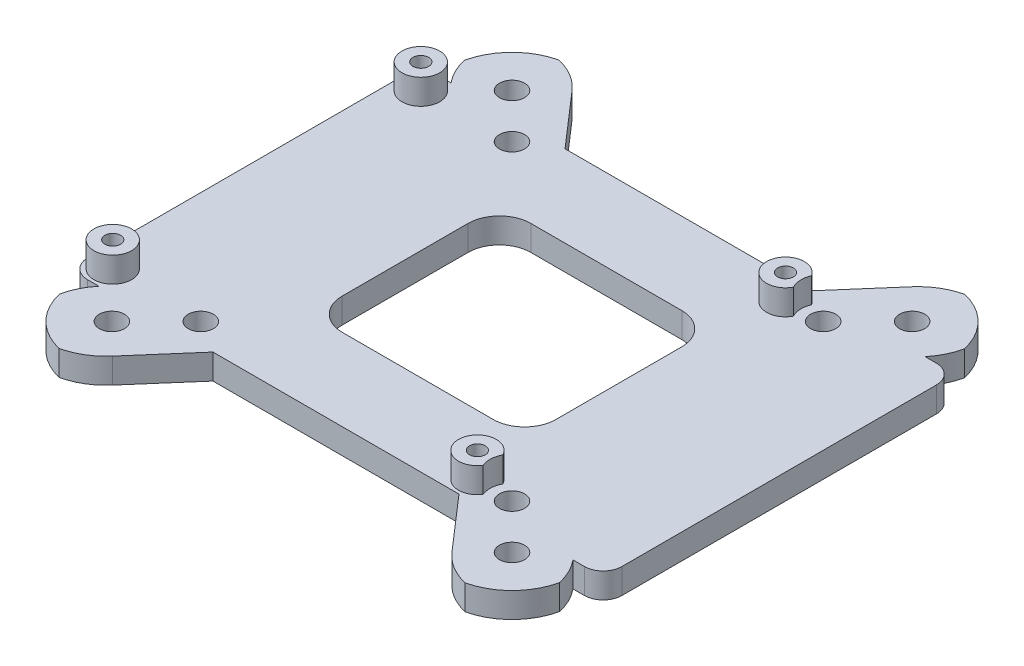
SolidWorks part; units mm, degrees
ref_plane "Front Plane" through (0, 0, 0) normal (0, 0, 1) x (1, 0, 0)
ref_plane "Top Plane" through (0, 0, 0) normal (0, 1, 0) x (1, 0, 0)
ref_plane "Right Plane" through (0, 0, 0) normal (1, 0, 0) x (0, 0, -1)
sketch "Sketch1" plane through (0, 0, 0) normal (0, 1, 0) x (1, 0, 0)
  line L1 (-42.5, -28) -> (42.5, -28)
  line L2 (-42.5, -28) -> (-42.5, 28)
  line L3 (-42.5, 28) -> (42.5, 28)
  line L4 (42.5, -28) -> (42.5, 28)
  line L5 (-12, -15) -> (12, -15)
  line L6 (-17, -10) -> (-17, 10)
  line L7 (-12, 15) -> (12, 15)
  line L8 (17, -10) -> (17, 10)
  line L9 (-17, -15) -> (17, 15) construction
  line L10 (-17, 15) -> (17, -15) construction
  circle A0 centre (-39, 24.5) radius 1.25
  circle A1 centre (-39, -24.5) radius 1.25
  circle A5 centre (19, 24.5) radius 1.25
  circle A6 centre (19, -24.5) radius 1.25
  arc A7 (-12, -15) -> (-17, -10) centre (-12, -10) cw
  arc A8 (12, -15) -> (17, -10) centre (12, -10) ccw
  arc A9 (17, 10) -> (12, 15) centre (12, 10) ccw
  arc A10 (-17, 10) -> (-12, 15) centre (-12, 10) cw
  point P0 (0, 0)
  point P14 (0, 0)
  dimension "D3" = 3.5
  dimension "D7" = 3.5
  dimension "D11" = 34
  dimension "D13" = 5
  dimension "D1" = 85
  dimension "D2" = 56
  dimension "D4" = 3.5
  dimension "D5" = 3.5
  dimension "D6" = 3.5
  dimension "D8" = 3.5
  dimension "D9" = 58
  dimension "D10" = 58
  dimension "D12" = 30
extrude "Boss-Extrude1" add sketch "Sketch1" along normal blind 4 contours L1 L4 L3 L2 region at (-41.4821, 0, 0)
sketch "Sketch2" plane through (0, 4, 0) normal (0, 1, 0) x (1, 0, 0)
  circle A0 centre (-39, 24.5) radius 3
  circle A1 centre (19, 24.5) radius 3
  circle A2 centre (19, -24.5) radius 3
  circle A3 centre (-39, -24.5) radius 3
  circle A4 centre (-39, 24.5) radius 1.25
  circle A5 centre (19, 24.5) radius 1.25
  circle A6 centre (19, -24.5) radius 1.25
  circle A7 centre (-39, -24.5) radius 1.25
extrude "Boss-Extrude2" add sketch "Sketch2" along normal blind 4
sketch "Sketch4" plane through (0, 4, 0) normal (0, 1, 0) x (1, 0, 0)
  line L1 (-40, -40) -> (40, -40)
  line L2 (-40, -40) -> (-40, 40)
  line L3 (-40, 40) -> (40, 40)
  line L4 (40, -40) -> (40, 40)
  line L5 (-40, -40) -> (40, 40) construction
  line L6 (-40, 40) -> (40, -40) construction
  point P0 (0, 0)
  dimension "D1" = 80
  dimension "D2" = 80
fillet "Fillet1" radius 3 4 edges at (42.5, 2, -28) (42.5, 2, 28) (-42.5, 2, 28) (-42.5, 2, -28)
sketch "Sketch5" plane through (0, 0, 0) normal (0, 1, 0) x (1, 0, 0)
  line L1 (15, -15) -> (-15, -15) construction
  line L2 (15, -15) -> (15, 15) construction
  line L3 (15, 15) -> (-15, 15) construction
  line L4 (-15, -15) -> (-15, 15) construction
  line L5 (15, -15) -> (-15, 15) construction
  line L6 (15, 15) -> (-15, -15) construction
  line L11 (-40, -30) -> (-17, -10)
  line L13 (-17, -10) -> (-17, 10)
  line L14 (-17, 10) -> (-40, 30)
  line L18 (10, 17) -> (30, 40)
  line L19 (-10, 17) -> (10, 17)
  line L20 (-30, 40) -> (-10, 17)
  line L22 (17, -10) -> (40, -30)
  line L23 (17, 10) -> (17, -10)
  line L24 (40, 30) -> (17, 10)
  line L26 (-10, -17) -> (-30, -40)
  line L27 (10, -17) -> (-10, -17)
  line L28 (30, -40) -> (10, -17)
  line L29 (-40, 30) -> (-40, 40)
  line L30 (-40, 40) -> (-30, 40)
  line L31 (30, 40) -> (40, 40)
  line L32 (40, 40) -> (40, 30)
  line L33 (40, -30) -> (40, -40)
  line L34 (40, -40) -> (30, -40)
  line L35 (-30, -40) -> (-40, -40)
  line L36 (-40, -40) -> (-40, -30)
  point P0 (0, 0)
  point P6 (-40, 0)
  point P32 (0, 0)
  dimension "D1" = 30
  dimension "D2" = 30
  dimension "D7" = 4
extrude "Boss-Extrude4" add sketch "Sketch5" along normal blind 4
sketch "Sketch3" plane through (0, 4, 0) normal (0, 1, 0) x (1, 0, 0)
  line L1 (-31.8198, -31.8198) -> (31.8198, -31.8198) construction
  line L2 (-31.8198, -31.8198) -> (-31.8198, 31.8198) construction
  line L3 (-31.8198, 31.8198) -> (31.8198, 31.8198) construction
  line L4 (31.8198, -31.8198) -> (31.8198, 31.8198) construction
  line L5 (-31.8198, -31.8198) -> (31.8198, 31.8198) construction
  line L6 (-31.8198, 31.8198) -> (31.8198, -31.8198) construction
  line L7 (-24.7487, -24.7487) -> (24.7487, -24.7487) construction
  line L8 (-24.7487, -24.7487) -> (-24.7487, 24.7487) construction
  line L9 (-24.7487, 24.7487) -> (24.7487, 24.7487) construction
  line L10 (24.7487, -24.7487) -> (24.7487, 24.7487) construction
  line L11 (-24.7487, -24.7487) -> (24.7487, 24.7487) construction
  line L12 (-24.7487, 24.7487) -> (24.7487, -24.7487) construction
  line L13 (12, -15) -> (-12, -15)
  line L14 (17, -10) -> (17, 10)
  line L15 (12, 15) -> (-12, 15)
  line L16 (-17, -10) -> (-17, 10)
  line L17 (17, -15) -> (-17, 15) construction
  line L18 (17, 15) -> (-17, -15) construction
  circle A0 centre (-31.8198, 31.8198) radius 2
  circle A1 centre (-24.7487, 24.7487) radius 2
  circle A2 centre (31.8198, 31.8198) radius 2
  circle A3 centre (24.7487, 24.7487) radius 2
  circle A4 centre (24.7487, -24.7487) radius 2
  circle A5 centre (31.8198, -31.8198) radius 2
  circle A6 centre (-31.8198, -31.8198) radius 2
  circle A7 centre (-24.7487, -24.7487) radius 2
  arc A8 (-12, 15) -> (-17, 10) centre (-12, 10) ccw
  arc A9 (-12, -15) -> (-17, -10) centre (-12, -10) cw
  arc A10 (12, -15) -> (17, -10) centre (12, -10) ccw
  arc A11 (17, 10) -> (12, 15) centre (12, 10) ccw
  point P0 (0, 0)
  point P6 (0, 0)
  point P19 (0, 0)
  dimension "D4" = 30
  dimension "D5" = 5
  dimension "D1" = 35
  dimension "D2" = 45
  dimension "D3" = 34
extrude "Cut-Extrude1" cut sketch "Sketch3" against normal through all
fillet "Fillet2" radius 10 12 edges at (-40, 2, -30) (-40, 2, -40) (-30, 2, -40) (30, 2, -40) (40, 2, -40) (40, 2, -30) (40, 2, 30) (40, 2, 40) (30, 2, 40) (-40, 2, 30) (-30, 2, 40) (-40, 2, 40)
sketch "Sketch6" plane through (0, 4, 0) normal (0, 1, 0) x (1, 0, 0)
  circle A0 centre (19, -24.5) radius 1.25
  circle A1 centre (19, 24.5) radius 1.25
extrude "Cut-Extrude2" cut sketch "Sketch6" against normal blind 10
sketch "Sketch7" plane through (0, 4, 0) normal (0, 1, 0) x (1, 0, 0)
  circle A0 centre (24.7487, -24.7487) radius 3.5
  circle A1 centre (24.7487, 24.7487) radius 3.5
extrude "Cut-Extrude3" cut sketch "Sketch7" along normal blind 10
